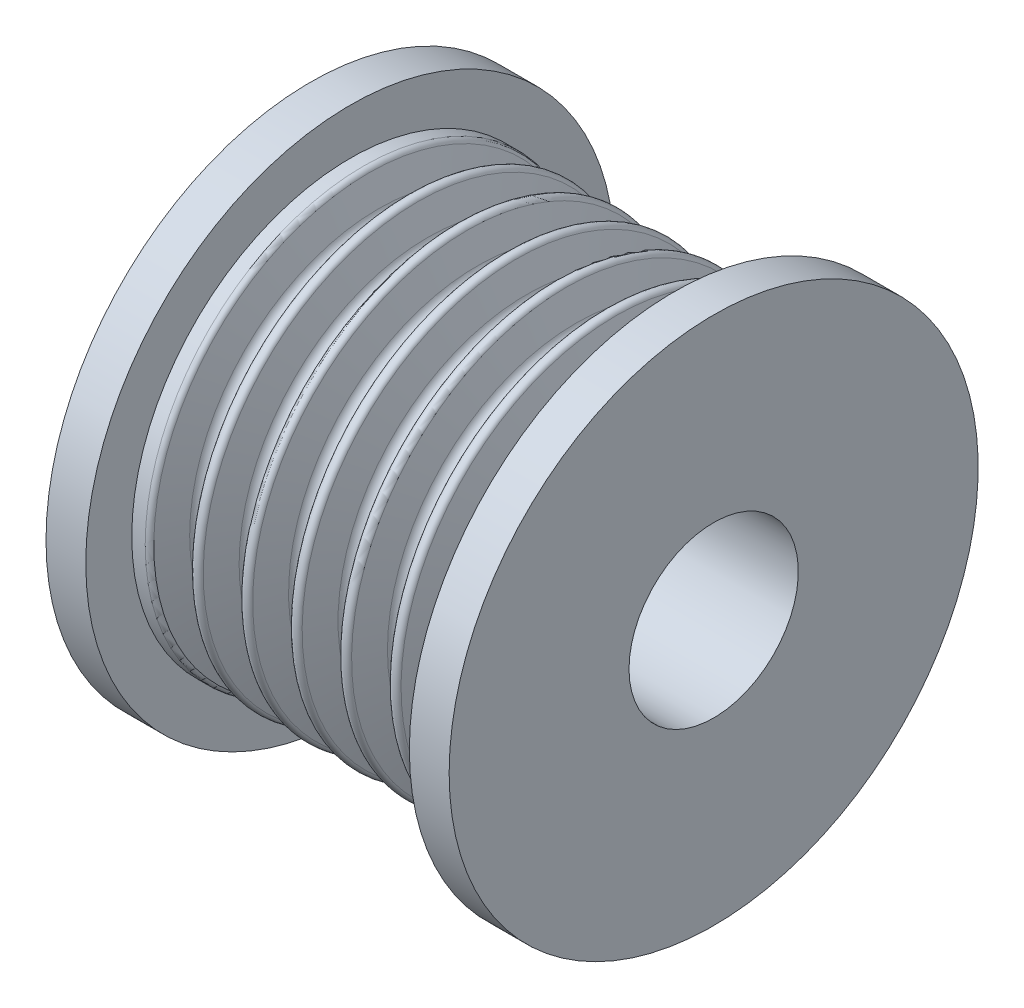
SolidWorks part; units mm, degrees
ref_plane "Front Plane" through (0, 0, 0) normal (0, 0, 1) x (1, 0, 0)
ref_plane "Top Plane" through (0, 0, 0) normal (0, 1, 0) x (1, 0, 0)
ref_plane "Right Plane" through (0, 0, 0) normal (1, 0, 0) x (0, 0, -1)
sketch "Sketch1" plane through (0, 0, 0) normal (0, 0, 1) x (1, 0, 0)
  line L2 (0, 5) -> (5, 5)
  line L3 (5, 5) -> (5, 12.5)
  line L4 (5, 12.5) -> (24.05, 12.5)
  line L5 (24.05, 12.5) -> (24.05, 4)
  line L10 (0, 0) -> (24, 0) construction
  line L11 (0, 5) -> (0, 4)
  line L12 (0, 4) -> (24.05, 4)
  dimension "D1" = 19.05
  dimension "D2" = 8
  dimension "D3" = 25
  dimension "D4" = 5
  dimension "D5" = 10
revolve "Revolve1" add sketch "Sketch1" angle 360 about L10
sketch "Sketch2" plane through (0, 0, 0) normal (0, 0, 1) x (1, 0, 0)
  line L0 (24.05, 0) -> (5, 0) construction
  line L1 (24.05, -12.5) -> (24.05, 12.5) construction
  line L2 (5, 5) -> (5, -5) construction
  line L3 (14.525, 0) -> (14.525, 12.5) construction
  line L4 (24.05, 12.5) -> (5, 12.5) construction
  line L5 (19.1986, 12.5) -> (21.5354, 12.5)
  line L6 (19.1986, 12.5) -> (19.1986, 10.3271)
  line L7 (21.5354, 12.5) -> (21.5354, 10.3271)
  line L8 (19.1986, 11.43) -> (21.5354, 11.43) construction
  line L9 (19.4373, 10.16) -> (19.8896, 8.9172)
  line L11 (20.8444, 8.9172) -> (21.2967, 10.16)
  line L12 (19.4373, 10.16) -> (21.2967, 10.16) construction
  line L13 (14.525, 12.5) -> (16.8618, 12.5) construction
  line L14 (16.8618, 12.5) -> (19.1986, 12.5) construction
  arc A0 (19.1986, 10.3271) -> (19.4373, 10.16) centre (19.1986, 10.0731) cw
  arc A1 (19.8896, 8.9172) -> (20.8444, 8.9172) centre (20.367, 9.0909) ccw
  arc A2 (21.5354, 10.3271) -> (21.2967, 10.16) centre (21.5354, 10.0731) ccw
  dimension "D3" = 0.254
  dimension "D6" = 0.508
  dimension "D1" = 2.3368
  dimension "D2" = 11.43
  dimension "D4" = 40
  dimension "D5" = 1.27
revolve "Cut-Revolve1" cut sketch "Sketch2" angle 360 about L0
pattern_linear "LPattern1" count 6 spacing 2.3368 along (-1, 0, 0) of "Cut-Revolve1"
sketch "Sketch3" plane through (0, 0, 0) normal (0, 0, 1) x (1, 0, 0)
  line L0 (24.05, 12.5) -> (21.5354, 12.5) construction
  line L2 (21.5354, 10.3271) -> (22.1704, 10.3271)
  line L4 (21.5354, 10.3271) -> (21.5354, 12.5)
  line L5 (21.5354, 12.5) -> (22.1704, 12.5)
  line L6 (22.1704, 10.3271) -> (22.1704, 12.5)
  line L7 (20.367, 8.5829) -> (20.367, 11.0958) construction
  line L8 (14.525, 10.3271) -> (14.525, 13.0355) construction
  line L9 (6.8796, 10.3271) -> (6.8796, 12.5)
  line L10 (7.5146, 12.5) -> (6.8796, 12.5)
  line L11 (7.5146, 10.3271) -> (7.5146, 12.5)
  line L12 (7.5146, 10.3271) -> (6.8796, 10.3271)
  line L13 (0, 0) -> (19.4427, 0) construction
  line L14 (0, 5) -> (0, -5) construction
  line L16 (21.5354, 10.3271) -> (21.5354, -10.3271) construction
  line L17 (21.5354, 10.3271) -> (21.5354, -10.3271) construction
  arc A3 (14.7637, 10.16) -> (14.2863, 10.16) centre (14.525, 10.0731) ccw construction
  arc A4 (19.8896, 8.9172) -> (20.8444, 8.9172) centre (20.367, 9.0909) ccw construction
  point P9 (18.367, 8.5829)
  point P14 (11.3566, 8.5829)
  point P15 (12.525, 10.3271)
  point P28 (19.9457, 10.5862)
  point P29 (0, 0)
  point P30 (19.6626, 10.3513)
  point P31 (19.4708, 10.3877)
  point P33 (20.1704, 10.685)
  point P35 (0, 0)
  dimension "D1" = 1.8034
revolve "Cut-Revolve2" cut sketch "Sketch3" angle 360 about L13
ref_plane "Plane1" through (0, 0, -12.5) normal (0, 0, -1) x (-1, 0, 0)
sketch "Sketch4" plane through (0, 0, -12.5) normal (0, 0, -1) x (-1, 0, 0)
  line L0 (-5, 0) -> (-24.05, 0) construction
  line L1 (-5, -12.5) -> (-5, 12.5) construction
  line L2 (-24.05, 12.5) -> (-24.05, -12.5) construction
  circle A0 centre (-14.525, 0) radius 2.5 construction
  point P8 (-11.8825, 0)
  point P9 (-11.8825, 0)
  point P10 (-14.525, 0)
  point P11 (-14.525, 0)
  dimension "D1" = 5
hole_wizard "M5x0.8 Tapped Hole1" positions "Sketch4" profile "Sketch6" tap size "M5x0.8" standard "ANSI Metric" end condition up to next
sketch "Sketch6" plane through (14.525, 0, -12.5) normal (1, 0, 0) x (0, 1, 0)
  line L0 (0, 0) -> (0, 8.5)
  line L1 (0, 8.5) -> (2.1, 8.5)
  line L2 (2.1, 8.5) -> (2.1, 0)
  line L5 (2.1, 0) -> (0, 0)
  line L11 (0, -6.35) -> (0, 107.95) construction
  dimension "Thru Tap Drill Dia." = 4.2
  dimension "Thru Tap Drill Depth" = 8.5
pattern_circular "CirPattern1" count 2 every 90 about axis through (5, 0, 0) along (-1, 0, 0) of "M5x0.8 Tapped Hole1"
fillet "Fillet1" radius 1 1 edges at (5, 0, 5)
equation "\"D1@Sketch1\"=0.75in"
equation "\"D1@Sketch2\"=0.092in"
equation "\"D2@Sketch2\"=0.9in/2"
equation "\"D3@Sketch2\"=0.01in"
equation "\"D6@Sketch2\"=0.02in"
equation "\"D5@Sketch2\"=0.05in"
equation "\"D3@LPattern1\"=0.092in"
equation "\"D4@LPattern1\"=0.092in"
equation "\"D1@Sketch3\"=0.071in"
